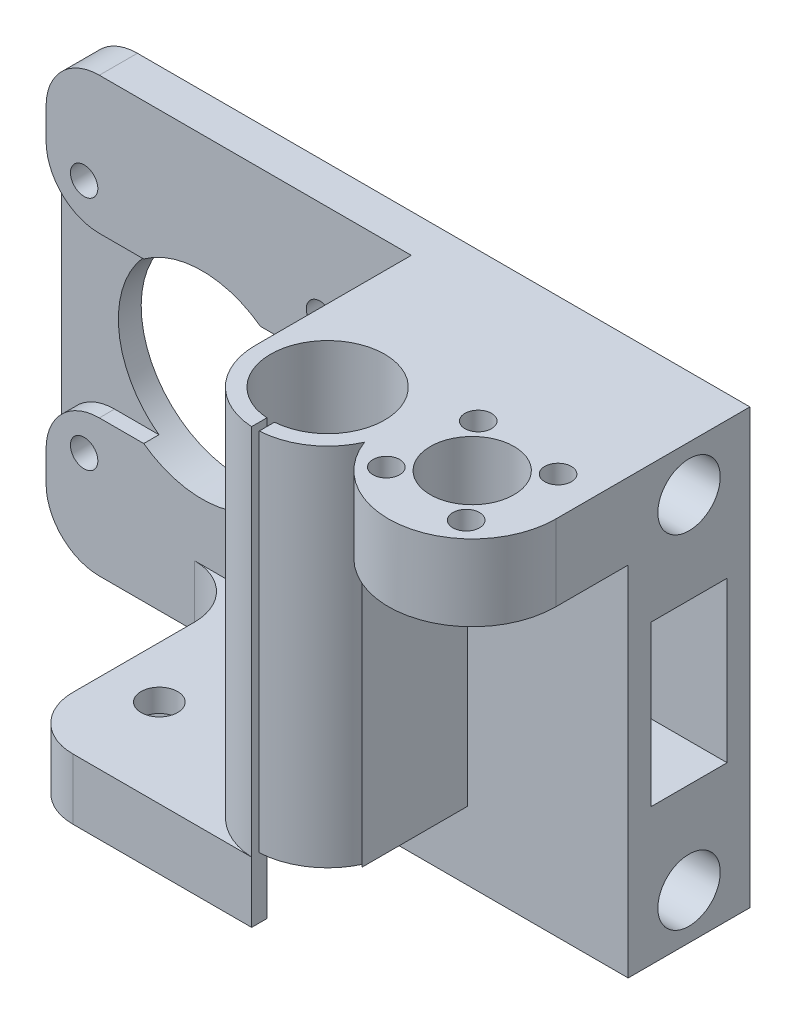
SolidWorks part; units mm, degrees
material "ABS"
ref_plane "Front Plane" through (0, 0, 0) normal (0, 0, 1) x (1, 0, 0)
ref_plane "Top Plane" through (0, 0, 0) normal (0, 1, 0) x (1, 0, 0)
ref_plane "Right Plane" through (0, 0, 0) normal (1, 0, 0) x (0, 0, -1)
sketch "Sketch2" plane through (0, 0, 0) normal (0, 1, 0) x (1, 0, 0)
  line L0 (0, 0) -> (0, -5)
  line L1 (0, -5) -> (48, -5)
  line L2 (48, -5) -> (48, -25.5)
  line L3 (57.5, -25.5) -> (48, -25.5) construction
  line L4 (87.5, -25.5) -> (87.5, 0)
  line L5 (87.5, 0) -> (0, 0)
  line L6 (57.5, -25.5) -> (76.5, -25.5) construction
  line L7 (66.1908, -29.3367) -> (66.1908, -25.5) construction
  line L8 (71.2515, -19.4623) -> (81.7485, -31.5377) construction
  line L9 (82.5377, -20.2515) -> (70.4623, -30.7485) construction
  line L10 (57.5, -25.5) -> (57.5, -34.9868) construction
  line L11 (57, -34.9868) -> (57.5, -34.9868) construction
  line L12 (57.5, -34.9868) -> (58, -34.9868) construction
  line L13 (57, -34.9868) -> (57, -32.9833)
  line L15 (58, -34.9868) -> (58, -32.9833)
  arc A0 (48, -25.5) -> (57, -34.9868) centre (57.5, -25.5) ccw
  circle A1 centre (76.5, -25.5) radius 5.5
  arc A2 (58, -32.9833) -> (57, -32.9833) centre (57.5, -25.5) ccw
  arc A3 (66.1908, -29.3367) -> (87.5, -25.5) centre (76.5, -25.5) ccw
  circle A4 centre (76.5, -25.5) radius 8 construction
  circle A5 centre (70.4623, -30.7485) radius 1.75
  circle A6 centre (82.5377, -20.2515) radius 1.75
  circle A7 centre (71.2515, -19.4623) radius 1.75
  circle A8 centre (81.7485, -31.5377) radius 1.75
  arc A9 (58, -34.9868) -> (66.1908, -29.3367) centre (57.5, -25.5) ccw
  dimension "D5" = 2
  dimension "D8" = 11
  dimension "D9" = 15
  dimension "D10" = 16
  dimension "D1" = 5.5
  dimension "D12" = 41
  dimension "D13" = 3.5
  dimension "D2" = 48
  dimension "D3" = 5
  dimension "D4" = 20.5
  dimension "D7" = 19
  dimension "D14" = 1
extrude "Boss-Extrude1" add sketch "Sketch2" along normal mid plane 57 contours L15 A9 A3 L4 L5 L0 L1 L2 A0 L13 A2 A1 A5 A6 A7 A8 region at (60.1326, 0, 12.0983)
sketch "Sketch3" plane through (0, 0, 0) normal (0, 0, 1) x (1, 0, 0)
  line L0 (0, 0) -> (88, 0) construction
  line L1 (66.4, 18.5) -> (88, 18.5)
  line L2 (66.4, 18.5) -> (66.4, -19.5)
  line L4 (88, 18.5) -> (88, -28.5)
  line L8 (57.1, -19.5) -> (66.4, -19.5)
  line L9 (57.1, -19.5) -> (57.1, -28.5)
  line L10 (57.1, -28.5) -> (88, -28.5)
  dimension "D4" = 47
  dimension "D1" = 88
  dimension "D2" = 18.5
  dimension "D3" = 21.6
  dimension "D5" = 9
  dimension "D6" = 9.3
extrude "Cut-Extrude1" cut sketch "Sketch3" along normal through all from offset 16
sketch "Sketch4" plane through (0, 0, 0) normal (0, 0, 1) x (1, 0, 0)
  line L0 (5, 15.5) -> (36, 15.5) construction
  line L1 (36, 15.5) -> (36, -15.5) construction
  line L2 (36, -15.5) -> (5, -15.5) construction
  line L3 (5, -15.5) -> (5, 15.5) construction
  line L4 (5, -15.5) -> (36, 15.5) construction
  circle A0 centre (5, 15.5) radius 1.8
  circle A1 centre (36, 15.5) radius 1.8
  circle A2 centre (5, -15.5) radius 1.8
  circle A3 centre (36, -15.5) radius 1.8
  circle A4 centre (20.5, 0) radius 13
  dimension "D1" = 31
  dimension "D2" = 3.6
  dimension "D5" = 26
  dimension "D3" = 15.5
  dimension "D4" = 5
extrude "Holes-for-motor" cut sketch "Sketch4" along normal through all
sketch "Sketch5" plane through (0, 0, 0) normal (0, 1, 0) x (1, 0, 0)
  line L0 (57.5, -34.9868) -> (57, -34.9868) construction
  line L1 (26.5, -34.9868) -> (26.5, -4.9868)
  line L2 (57.5, -25.5) -> (57.5, -34.9868) construction
  line L3 (26.5, -4.9868) -> (48, -4.9868)
  line L4 (48, -25.5) -> (48, -4.9868)
  line L5 (26.5, -34.9868) -> (57, -34.9868)
  circle A0 centre (57.5, -25.5) radius 9.5
  dimension "D2" = 19
  dimension "D1" = 31
  dimension "D3" = 57.5
  dimension "D4" = 25.5
  dimension "D5" = 30
  dimension "D6" = 0.5
extrude "Boss-Extrude2" add sketch "Sketch5" against normal blind 8 from offset 20.5 contours A0 L4 L3 L1 region at (37.6225, 0, 20.36) offset against normal yes
sketch "Sketch6" plane through (0, 0, 0) normal (1, 0, 0) x (0, 0, -1)
  line L0 (-3, 0) -> (0, 0) construction
  line L1 (-13, 10.5) -> (-3, 10.5)
  line L2 (-13, 10.5) -> (-13, -10.5)
  line L3 (-13, -10.5) -> (-3, -10.5)
  line L4 (-3, 10.5) -> (-3, -10.5)
  dimension "D1" = 10
  dimension "D2" = 21
  dimension "D3" = 3
extrude "Cut-Extrude3" cut sketch "Sketch6" along normal through all
hole_wizard "M4 Clearance Hole1" positions "Sketch8" profile "Sketch9" hole size "M4" standard "ANSI Metric" end condition through all
sketch "Sketch8" plane through (0, -20.5, 0) normal (0, 1, 0) x (1, 0, 0)
  line L0 (26.5, -34.9868) -> (57, -34.9868) construction
  line L2 (26.5, -34.9868) -> (26.5, -5) construction
  point P0 (33.2838, -23.3998)
  dimension "D1" = 11.587
  dimension "D2" = 6.7838
sketch "Sketch9" plane through (33.2838, -20.5, 23.3998) normal (1, 0, 0) x (0, 0, 1)
  line L0 (0, 0) -> (0, 8)
  line L1 (0, 8) -> (2.4, 8)
  line L2 (2.4, 8) -> (2.4, 0)
  line L5 (2.4, 0) -> (0, 0)
  line L11 (0, -6.35) -> (0, 107.95) construction
  dimension "Thru Hole Dia." = 4.8
  dimension "Thru Hole Depth" = 8
sketch "Sketch10" plane through (0, -20.5, 0) normal (0, 1, 0) x (1, 0, 0)
  line L0 (33.2838, -23.3998) -> (35.6838, -23.3998) construction
  line L1 (39.8407, -23.3998) -> (37.7623, -19.7998)
  line L2 (37.7623, -19.7998) -> (22.7623, -19.7998)
  line L5 (22.7623, -26.9998) -> (37.7623, -26.9998)
  line L6 (37.7623, -26.9998) -> (39.8407, -23.3998)
  line L7 (22.7623, -26.9998) -> (22.7623, -19.7998)
  line L10 (33.0053, -20.8391) -> (31.9661, -22.6391) [skipped]
  line L11 (31.9661, -24.1606) -> (33.0053, -25.9606) [skipped]
  circle A0 centre (35.6838, -23.3998) radius 3.6 construction
  circle A1 centre (33.2838, -23.3998) radius 2.4 construction
  dimension "D1" = 7.2
  dimension "D2" = 15
extrude "Cut-Extrude6" cut sketch "Sketch10" against normal blind 3.4 from offset 3 offset against normal yes
fillet "Fillet1" radius 7 6 edges at (0, -28.5, 2.5) (0, 28.5, 2.5) (26.5, -24.5, 34.9868) (0, 10.5, 4) (0, -10.5, 4) (26.5, -24.5, 5)
sketch "Sketch11" plane through (87.5, 0, 0) normal (1, 0, 0) x (0, 0, -1)
  line L0 (-8, 0) -> (-8, 22.5) construction
  line L1 (-8, -22.5) -> (-8, 0) construction
  line L2 (0, 0) -> (-8, 0) construction
  line L3 (-8, -22.5) -> (-8, -28.5) construction
  line L5 (-16, -28.5) -> (0, -28.5) construction
  circle A0 centre (-8, -22.5) radius 4.1
  circle A1 centre (-8, 22.5) radius 4.1
  point P4 (0, 0)
  dimension "D1" = 45
  dimension "D2" = 8.2
extrude "Cut-Extrude7" cut sketch "Sketch11" against normal blind 30
